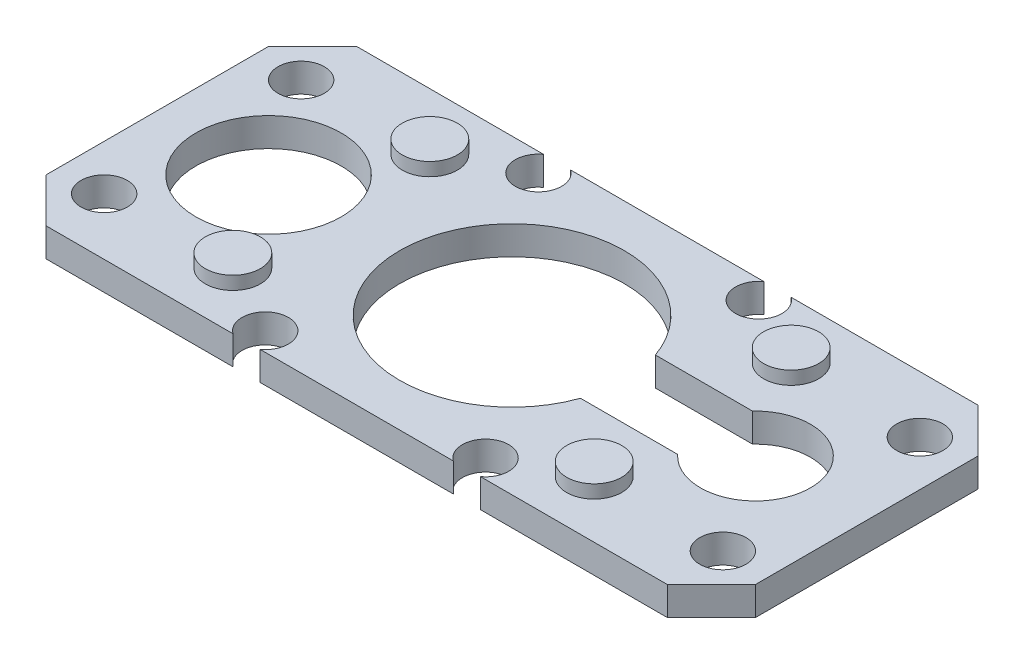
SolidWorks part; units mm, degrees
ref_plane "Front" through (0, 0, 0) normal (0, 0, 1) x (1, 0, 0)
ref_plane "Top" through (0, 0, 0) normal (0, 1, 0) x (1, 0, 0)
ref_plane "Right" through (0, 0, 0) normal (1, 0, 0) x (0, 0, -1)
sketch "Sketch1" plane through (0, 0, 0) normal (0, 1, 0) x (1, 0, 0)
  line L0 (-5.5671, 8.9535) -> (5.5671, 8.9535)
  line L1 (-6.35, -7.874) -> (6.35, -7.874) construction
  line L2 (-6.35, -7.874) -> (-6.35, 7.874) construction
  line L3 (-6.35, 7.874) -> (6.35, 7.874) construction
  line L4 (6.35, -7.874) -> (6.35, 7.874) construction
  line L5 (-6.35, -7.874) -> (6.35, 7.874) construction
  line L6 (-6.35, 7.874) -> (6.35, -7.874) construction
  line L7 (-17.8308, -5.6769) -> (17.8308, -5.6769) construction
  line L8 (-17.8308, -5.6769) -> (-17.8308, 5.6769) construction
  line L9 (-17.8308, 5.6769) -> (17.8308, 5.6769) construction
  line L10 (17.8308, -5.6769) -> (17.8308, 5.6769) construction
  line L11 (-17.8308, -5.6769) -> (17.8308, 5.6769) construction
  line L12 (-17.8308, 5.6769) -> (17.8308, -5.6769) construction
  line L13 (-10.414, -5.6769) -> (10.414, -5.6769) construction
  line L14 (-10.414, -5.6769) -> (-10.414, 5.6769) construction
  line L15 (-10.414, 5.6769) -> (10.414, 5.6769) construction
  line L16 (10.414, -5.6769) -> (10.414, 5.6769) construction
  line L17 (-10.414, -5.6769) -> (10.414, 5.6769) construction
  line L18 (-10.414, 5.6769) -> (10.414, -5.6769) construction
  line L19 (-20.447, -8.9535) -> (-7.1329, -8.9535)
  line L20 (-20.447, -8.9535) -> (-20.447, 8.9535)
  line L21 (-20.447, 8.9535) -> (-7.1329, 8.9535)
  line L22 (20.447, -8.9535) -> (20.447, 8.9535)
  line L23 (-20.447, -8.9535) -> (20.447, 8.9535) construction
  line L24 (-20.447, 8.9535) -> (20.447, -8.9535) construction
  line L25 (7.1329, 8.9535) -> (20.447, 8.9535)
  line L26 (7.1329, -8.9535) -> (20.447, -8.9535)
  line L27 (-5.5671, -8.9535) -> (5.5671, -8.9535)
  circle A0 centre (-17.8308, 5.6769) radius 1.3335
  arc A1 (-7.1329, 8.9535) -> (-5.5671, 8.9535) centre (-6.35, 7.874) ccw
  arc A2 (5.5671, 8.9535) -> (7.1329, 8.9535) centre (6.35, 7.874) ccw
  circle A3 centre (17.8308, 5.6769) radius 1.3335
  circle A4 centre (17.8308, -5.6769) radius 1.3335
  arc A5 (7.1329, -8.9535) -> (5.5671, -8.9535) centre (6.35, -7.874) ccw
  arc A6 (-5.5671, -8.9535) -> (-7.1329, -8.9535) centre (-6.35, -7.874) ccw
  circle A7 centre (-17.8308, -5.6769) radius 1.3335
  circle A8 centre (-10.414, 5.6769) radius 1.5875
  circle A9 centre (10.414, 5.6769) radius 1.5875
  circle A10 centre (10.414, -5.6769) radius 1.5875
  circle A11 centre (-10.414, -5.6769) radius 1.5875
  point P0 (0, 0)
  point P6 (0, 0)
  point P11 (0, 0)
  point P16 (0, 0)
  dimension "D8" = 2.667
  dimension "D9" = 3.175
  dimension "D1" = 12.7
  dimension "D2" = 15.748
  dimension "D3" = 11.3538
  dimension "D4" = 35.6616
  dimension "D5" = 40.894
  dimension "D6" = 17.907
  dimension "D7" = 20.828
extrude "Boss-Extrude1" add sketch "Sketch1" along normal blind 1.651
chamfer "Chamfer1" distance 2.54 angle 45 4 edges at (-20.447, 0.8255, 8.9535) (-20.447, 0.8255, -8.9535) (20.447, 0.8255, -8.9535) (20.447, 0.8255, 8.9535)
extrude "Boss-Extrude2" add sketch "Sketch1<2>" along normal blind 2.413 contours A8 | A9 | A10 | A11
sketch "Sketch1<2>" plane through (0, 0, 0) normal (0, 1, 0) x (1, 0, 0) same geometry as "Sketch1"
extrude "Cut-Extrude1" cut sketch "Sketch1<3>" along normal blind 0.889 contours A11 | A10 | A9 | A8
sketch "Sketch1<3>" plane through (0, 0, 0) normal (0, 1, 0) x (1, 0, 0) same geometry as "Sketch1"
sketch "Sketch5" plane through (0, 1.651, 0) normal (0, 1, 0) x (1, 0, 0)
  line L0 (-20.447, 0) -> (20.447, 0) construction
  line L1 (-20.447, 6.4135) -> (-20.447, -6.4135) construction
  line L2 (20.447, -6.4135) -> (20.447, 6.4135) construction
  line L3 (5.5671, 8.9535) -> (-5.5671, 8.9535) construction
  line L4 (-14.0335, -8.9535) -> (14.0335, -8.9535) construction
  line L5 (-14.0335, -8.9535) -> (-14.0335, 8.9535) construction
  line L6 (-14.0335, 8.9535) -> (14.0335, 8.9535) construction
  line L7 (14.0335, -8.9535) -> (14.0335, 8.9535) construction
  line L8 (-14.0335, -8.9535) -> (14.0335, 8.9535) construction
  line L9 (-14.0335, 8.9535) -> (14.0335, -8.9535) construction
  line L11 (6.1066, -2.159) -> (11.7056, -2.159)
  line L13 (6.1066, 2.159) -> (11.7056, 2.159)
  line L15 (6.1066, -2.159) -> (11.7056, 2.159) construction
  line L16 (6.1066, 2.159) -> (11.7056, -2.159) construction
  arc A0 (6.1066, 2.159) -> (6.1066, -2.159) centre (0, 0) ccw
  circle A1 centre (-14.0335, 0) radius 4.191
  arc A2 (11.7056, -2.159) -> (11.7056, 2.159) centre (14.0335, 0) ccw
  point P19 (8.9061, 0)
  dimension "D1" = 12.954
  dimension "D3" = 6.35
  dimension "D4" = 8.382
  dimension "D2" = 28.067
  dimension "D5" = 4.318
extrude "Cut-Extrude5" cut sketch "Sketch5" against normal through all
